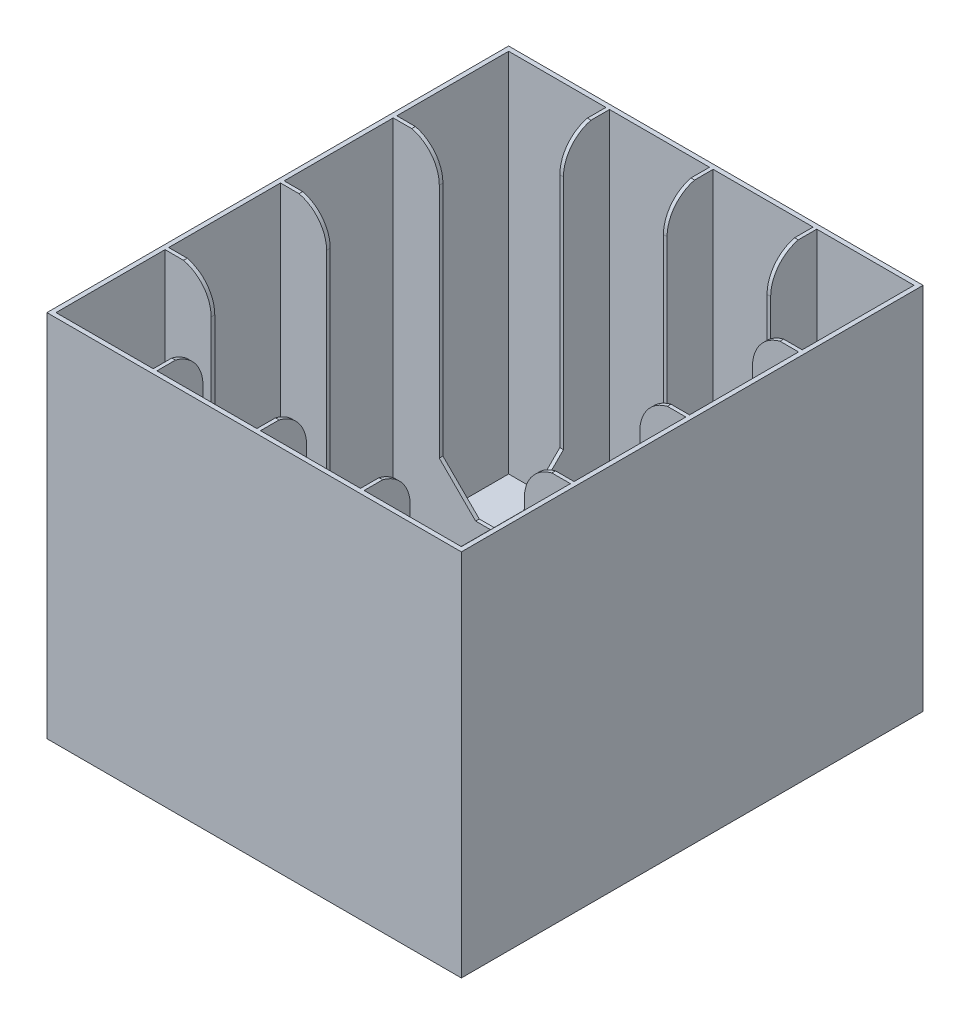
SolidWorks part; units mm, degrees
ref_plane "Front Plane" through (0, 0, 0) normal (0, 0, 1) x (1, 0, 0)
ref_plane "Top Plane" through (0, 0, 0) normal (0, 1, 0) x (1, 0, 0)
ref_plane "Right Plane" through (0, 0, 0) normal (1, 0, 0) x (0, 0, -1)
sketch "Sketch2" plane through (0, 0, 0) normal (0, 1, 0) x (1, 0, 0)
  line L0 (-619.0506, 406.7008) -> (-394.0506, 406.7008)
  line L1 (-620.5506, 408.2008) -> (-392.5506, 408.2008)
  line L2 (-620.5506, 408.2008) -> (-620.5506, 154.2008)
  line L3 (-620.5506, 154.2008) -> (-392.5506, 154.2008)
  line L4 (-392.5506, 408.2008) -> (-392.5506, 154.2008)
  line L5 (-394.0506, 406.7008) -> (-394.0506, 155.7008)
  line L6 (-619.0506, 155.7008) -> (-394.0506, 155.7008)
  line L7 (-619.0506, 406.7008) -> (-619.0506, 155.7008)
  line L8 (-506.5506, 406.7008) -> (-506.5506, 155.7008)
  line L9 (-619.0506, 281.2008) -> (-506.5506, 281.2008)
  line L10 (-506.5506, 281.2008) -> (-394.0506, 281.2008)
  line L11 (-619.0506, 343.2008) -> (-394.0506, 343.2008)
  line L12 (-619.0506, 217.7008) -> (-394.0506, 217.7008)
  line L13 (-563.5506, 406.7008) -> (-563.5506, 155.7008)
  line L14 (-449.5506, 155.7008) -> (-449.5506, 406.7008)
  line L15 (-618.0506, 405.7008) -> (-618.0506, 156.7008)
  line L16 (-618.0506, 156.7008) -> (-395.0506, 156.7008)
  line L17 (-395.0506, 405.7008) -> (-395.0506, 156.7008)
  line L18 (-618.0506, 405.7008) -> (-395.0506, 405.7008)
  line L19 (-562.5506, 406.7008) -> (-562.5506, 155.7008)
  line L20 (-619.0506, 344.2008) -> (-394.0506, 344.2008)
  line L21 (-505.5506, 406.7008) -> (-505.5506, 155.7008)
  line L22 (-619.0506, 282.2008) -> (-506.5506, 282.2008)
  line L23 (-506.5506, 282.2008) -> (-394.0506, 282.2008)
  line L24 (-450.5506, 155.7008) -> (-450.5506, 406.7008)
  line L25 (-619.0506, 218.7008) -> (-394.0506, 218.7008)
  line L26 (-620.0506, 407.7008) -> (-620.0506, 154.7008)
  line L27 (-620.0506, 154.7008) -> (-393.0506, 154.7008)
  line L28 (-393.0506, 407.7008) -> (-393.0506, 154.7008)
  line L29 (-620.0506, 407.7008) -> (-393.0506, 407.7008)
  line L30 (-564.5506, 406.7008) -> (-564.5506, 155.7008)
  line L31 (-619.0506, 342.2008) -> (-394.0506, 342.2008)
  line L32 (-507.5506, 406.7008) -> (-507.5506, 155.7008)
  line L33 (-619.0506, 280.2008) -> (-506.5506, 280.2008)
  line L34 (-506.5506, 280.2008) -> (-394.0506, 280.2008)
  line L35 (-448.5506, 155.7008) -> (-448.5506, 406.7008)
  line L36 (-619.0506, 216.7008) -> (-394.0506, 216.7008)
  dimension "D1" = 228
  dimension "D2" = 254
  dimension "D4" = 114
  dimension "D5" = 114
  dimension "D6" = 127
  dimension "D7" = 63.5
  dimension "D8" = 63.5
  dimension "D9" = 57
  dimension "D10" = 57
  dimension "D3" = 1.5
  dimension "D11" = 1
  dimension "D12" = 1
extrude "Boss-Extrude1" add sketch "Sketch2" against normal blind 1.6 contours L4 L3 L2 L1
extrude "Boss-Extrude2" add sketch "Sketch2<6>" along normal blind 202 contours L4 L1 L2 L3 L26 L29 L28 L27 | L29 L26 L27 L28 L7 L0 L5 L6 | L18 L24 L0 L21 | L32 L0 L19 L18 | L0 L32 L18 L8 | L21 L0 L8 L18 | L30 L0 L7 L20 L15 L18 | L0 L30 L18 L13 | L19 L0 L13 L18 | L20 L7 L11 L15 | L7 L31 L15 L11 | L31 L7 L22 L15 | L22 L7 L9 L15 | L7 L33 L15 L9 | L33 L7 L25 L15 | L25 L7 L12 L15 | L7 L36 L15 L12 | L36 L7 L6 L30 L16 L15 | L32 L16 L19 L6 | L19 L16 L13 L6 | L16 L30 L6 L13 | L16 L32 L6 L8 | L21 L16 L8 L6 | L6 L24 L16 L21 | L24 L6 L14 L16 | L6 L35 L16 L14 | L36 L17 L16 L35 L6 L5 | L17 L36 L5 L12 | L25 L17 L12 L5 | L34 L17 L25 L5 | L20 L17 L11 L5 | L17 L31 L5 L11 | L31 L17 L23 L5 | L35 L18 L17 L20 L5 L0 | L24 L18 L14 L0 | L18 L35 L0 L14 region at (-591.8006, 0, -405.8715) region at (-564.0506, 0, -406.2008) region at (-618.5506, 0, -343.7008) region at (-563.0506, 0, -406.2008) region at (-618.5506, 0, -342.7008) region at (-535.0506, 0, -406.2008) region at (-618.5506, 0, -312.2008) region at (-507.0506, 0, -406.2008) region at (-618.5506, 0, -281.7008) region at (-506.0506, 0, -406.2008) region at (-618.5506, 0, -280.7008) region at (-478.0506, 0, -406.2008) region at (-618.5506, 0, -249.4508) region at (-450.0506, 0, -406.2008) region at (-618.5506, 0, -218.2008) region at (-449.0506, 0, -406.2008) region at (-618.5506, 0, -217.2008) region at (-421.3006, 0, -405.8715) region at (-618.5506, 0, -215.8828) region at (-394.5506, 0, -343.7008) region at (-564.0506, 0, -156.2008) region at (-394.5506, 0, -342.7008) region at (-563.0506, 0, -156.2008) region at (-394.5506, 0, -312.2008) region at (-535.0506, 0, -156.2008) region at (-507.0506, 0, -156.2008) region at (-506.0506, 0, -156.2008) region at (-394.5506, 0, -249.4508) region at (-478.0506, 0, -156.2008) region at (-394.5506, 0, -218.2008) region at (-450.0506, 0, -156.2008) region at (-394.5506, 0, -217.2008) region at (-449.0506, 0, -156.2008) region at (-394.8686, 0, -186.2008) region at (-506.5506, 0, -407.8595) region at (-506.5506, 0, -407.3609)
sketch "Sketch2<6>" plane through (0, 0, 0) normal (0, 1, 0) x (1, 0, 0) same geometry as "Sketch2"
extrude "Boss-Extrude6" add sketch "Sketch2<7>" along normal blind 202 contours L36 L14 L16 L35 | L36 L24 L16 L14 region at (-450.0506, 0, -186.7008) region at (-449.0506, 0, -186.7008)
sketch "Sketch2<7>" plane through (0, 0, 0) normal (0, 1, 0) x (1, 0, 0) same geometry as "Sketch2"
extrude "Boss-Extrude7" add sketch "Sketch2<8>" along normal blind 202 contours L17 L34 L5 L10 | L23 L17 L10 L5 | L35 L10 L17 L23 | L35 L34 L17 L10 region at (-394.5506, 0, -281.7008) region at (-421.8006, 0, -281.7008) region at (-394.5506, 0, -280.7008) region at (-421.8006, 0, -280.7008)
sketch "Sketch2<8>" plane through (0, 0, 0) normal (0, 1, 0) x (1, 0, 0) same geometry as "Sketch2"
extrude "Boss-Extrude8" add sketch "Sketch2<9>" along normal blind 202 contours L35 L11 L17 L20 | L35 L31 L17 L11 | L11 L24 L20 L21 | L21 L31 L24 L11 | L24 L31 L14 L11 | L24 L11 L14 L20 | L11 L35 L20 L14 | L31 L35 L11 L14 region at (-478.0506, 0, -343.7008) region at (-450.0506, 0, -343.7008) region at (-478.0506, 0, -342.7008) region at (-449.0506, 0, -343.7008) region at (-450.0506, 0, -342.7008) region at (-421.8006, 0, -343.7008) region at (-449.0506, 0, -342.7008) region at (-421.8006, 0, -342.7008)
sketch "Sketch2<9>" plane through (0, 0, 0) normal (0, 1, 0) x (1, 0, 0) same geometry as "Sketch2"
extrude "Boss-Extrude12" add sketch "Sketch2<10>" along normal blind 202 contours L20 L35 L18 L14 | L24 L20 L14 L18 region at (-450.0506, 0, -374.9508) region at (-449.0506, 0, -374.9508)
sketch "Sketch2<10>" plane through (0, 0, 0) normal (0, 1, 0) x (1, 0, 0) same geometry as "Sketch2"
extrude "Boss-Extrude13" add sketch "Sketch2<11>" along normal blind 202 contours L23 L35 L31 L14 | L31 L24 L23 L14 | L10 L35 L23 L14 | L24 L10 L14 L23 | L24 L34 L14 L10 | L34 L24 L25 L14 | L25 L35 L34 L14 | L34 L35 L10 L14 region at (-450.0506, 0, -312.2008) region at (-449.0506, 0, -312.2008) region at (-450.0506, 0, -281.7008) region at (-449.0506, 0, -281.7008) region at (-450.0506, 0, -280.7008) region at (-449.0506, 0, -280.7008) region at (-450.0506, 0, -249.4508) region at (-449.0506, 0, -249.4508)
sketch "Sketch2<11>" plane through (0, 0, 0) normal (0, 1, 0) x (1, 0, 0) same geometry as "Sketch2"
extrude "Boss-Extrude14" add sketch "Sketch2<12>" along normal blind 202 contours L35 L12 L17 L25 | L35 L36 L17 L12 | L25 L24 L12 L14 | L24 L36 L14 L12 | L14 L36 L35 L12 | L12 L35 L25 L14 | L25 L21 L12 L24 | L21 L36 L24 L12 region at (-478.0506, 0, -218.2008) region at (-450.0506, 0, -218.2008) region at (-478.0506, 0, -217.2008) region at (-449.0506, 0, -218.2008) region at (-450.0506, 0, -217.2008) region at (-421.8006, 0, -218.2008) region at (-449.0506, 0, -217.2008) region at (-421.8006, 0, -217.2008)
sketch "Sketch2<12>" plane through (0, 0, 0) normal (0, 1, 0) x (1, 0, 0) same geometry as "Sketch2"
extrude "Boss-Extrude19" add sketch "Sketch2<13>" along normal blind 202 contours L10 L24 L23 L21 | L21 L34 L24 L10 | L22 L32 L9 L8 | L32 L33 L8 L9 | L8 L34 L21 L10 | L23 L8 L10 L21 region at (-507.0506, 0, -281.7008) region at (-506.0506, 0, -281.7008) region at (-507.0506, 0, -280.7008) region at (-478.0506, 0, -281.7008) region at (-506.0506, 0, -280.7008) region at (-478.0506, 0, -280.7008)
sketch "Sketch2<13>" plane through (0, 0, 0) normal (0, 1, 0) x (1, 0, 0) same geometry as "Sketch2"
extrude "Boss-Extrude25" add sketch "Sketch2<14>" along normal blind 202 contours L34 L8 L25 L21 | L33 L32 L25 L8 | L25 L8 L12 L21 | L25 L32 L12 L8 | L32 L36 L8 L12 | L8 L36 L21 L12 region at (-507.0506, 0, -249.4508) region at (-506.0506, 0, -249.4508) region at (-507.0506, 0, -218.2008) region at (-506.0506, 0, -218.2008) region at (-507.0506, 0, -217.2008) region at (-506.0506, 0, -217.2008)
sketch "Sketch2<14>" plane through (0, 0, 0) normal (0, 1, 0) x (1, 0, 0) same geometry as "Sketch2"
extrude "Boss-Extrude26" add sketch "Sketch2<17>" along normal blind 202 contours L36 L8 L16 L21 | L36 L32 L16 L8 | L19 L36 L32 L12 | L32 L25 L19 L12 region at (-535.0506, 0, -218.2008) region at (-535.0506, 0, -217.2008) region at (-507.0506, 0, -186.7008) region at (-506.0506, 0, -186.7008)
sketch "Sketch2<17>" plane through (0, 0, 0) normal (0, 1, 0) x (1, 0, 0) same geometry as "Sketch2"
extrude "Boss-Extrude27" add sketch "Sketch2<18>" along normal blind 202 contours L33 L13 L25 L19 | L33 L30 L25 L13 | L25 L30 L12 L13 | L25 L13 L12 L19 | L13 L36 L19 L12 | L30 L36 L13 L12 | L36 L30 L16 L13 | L36 L13 L16 L19 region at (-564.0506, 0, -249.4508) region at (-563.0506, 0, -249.4508) region at (-564.0506, 0, -218.2008) region at (-563.0506, 0, -218.2008) region at (-564.0506, 0, -217.2008) region at (-563.0506, 0, -217.2008) region at (-564.0506, 0, -186.7008) region at (-563.0506, 0, -186.7008)
sketch "Sketch2<18>" plane through (0, 0, 0) normal (0, 1, 0) x (1, 0, 0) same geometry as "Sketch2"
extrude "Boss-Extrude36" add sketch "Sketch2<21>" along normal blind 202 contours L15 L33 L30 L9 | L30 L22 L15 L9 | L30 L33 L13 L9 | L22 L30 L9 L13 region at (-591.3006, 0, -281.7008) region at (-564.0506, 0, -281.7008) region at (-591.3006, 0, -280.7008) region at (-564.0506, 0, -280.7008)
sketch "Sketch2<21>" plane through (0, 0, 0) normal (0, 1, 0) x (1, 0, 0) same geometry as "Sketch2"
extrude "Boss-Extrude40" add sketch "Sketch2<23>" along normal blind 202 contours L19 L33 L32 L9 | L32 L22 L19 L9 | L31 L32 L22 L8 | L31 L8 L23 L21 | L8 L31 L21 L11 | L21 L20 L8 L11 | L20 L32 L11 L8 | L11 L32 L31 L8 | L32 L11 L19 L31 | L32 L20 L19 L11 | L21 L18 L8 L20 | L18 L32 L20 L8 | L21 L0 L8 L18 | L0 L32 L18 L8 | L22 L13 L9 L19 | L13 L33 L19 L9 region at (-507.0506, 0, -406.2008) region at (-506.0506, 0, -406.2008) region at (-507.0506, 0, -374.9508) region at (-535.0506, 0, -343.7008) region at (-506.0506, 0, -374.9508) region at (-507.0506, 0, -343.7008) region at (-535.0506, 0, -342.7008) region at (-506.0506, 0, -343.7008) region at (-507.0506, 0, -342.7008) region at (-563.0506, 0, -281.7008) region at (-506.0506, 0, -342.7008) region at (-507.0506, 0, -312.2008) region at (-535.0506, 0, -281.7008) region at (-563.0506, 0, -280.7008) region at (-506.0506, 0, -312.2008) region at (-535.0506, 0, -280.7008)
sketch "Sketch2<23>" plane through (0, 0, 0) normal (0, 1, 0) x (1, 0, 0) same geometry as "Sketch2"
extrude "Boss-Extrude41" add sketch "Sketch2<24>" along normal blind 202 contours L15 L36 L30 L12 | L30 L25 L15 L12 | L15 L31 L30 L11 | L30 L20 L15 L11 | L20 L30 L11 L13 | L30 L31 L13 L11 | L13 L31 L19 L11 | L20 L13 L11 L19 | L13 L20 L19 L18 | L18 L30 L20 L13 | L31 L30 L22 L13 | L31 L13 L22 L19 region at (-564.0506, 0, -374.9508) region at (-591.3006, 0, -343.7008) region at (-563.0506, 0, -374.9508) region at (-564.0506, 0, -343.7008) region at (-591.3006, 0, -342.7008) region at (-563.0506, 0, -343.7008) region at (-564.0506, 0, -342.7008) region at (-563.0506, 0, -342.7008) region at (-564.0506, 0, -312.2008) region at (-563.0506, 0, -312.2008) region at (-591.3006, 0, -218.2008) region at (-591.3006, 0, -217.2008)
sketch "Sketch2<24>" plane through (0, 0, 0) normal (0, 1, 0) x (1, 0, 0) same geometry as "Sketch2"
sketch "Sketch3" plane through (0, 202, 0) normal (0, 1, 0) x (1, 0, 0)
  line L0 (-392.5506, 408.2008) -> (-392.5506, 154.2008) construction
  line L1 (-592.7033, 380.3534) -> (-420.398, 380.3534)
  line L2 (-592.7033, 380.3534) -> (-592.7033, 182.0481)
  line L3 (-592.7033, 182.0481) -> (-420.398, 182.0481)
  line L4 (-420.398, 380.3534) -> (-420.398, 182.0481)
  line L5 (-620.5506, 408.2008) -> (-620.5506, 154.2008) construction
  line L6 (-620.5506, 408.2008) -> (-392.5506, 408.2008) construction
  line L7 (-620.5506, 154.2008) -> (-392.5506, 154.2008) construction
  dimension "D1" = 27.8473
  dimension "D2" = 27.8473
  dimension "D3" = 27.8473
  dimension "D4" = 27.8473
extrude "Cut-Extrude1" cut sketch "Sketch3" against normal blind 170
chamfer "Chamfer1" distance 20 distance2 20 12 edges at (-563.5506, 32, -182.0481) (-506.5506, 32, -182.0481) (-449.5506, 32, -182.0481) (-420.398, 32, -217.7008) (-420.398, 32, -281.2008) (-420.398, 32, -343.2008) (-592.7033, 32, -217.7008) (-592.7033, 32, -281.2008) (-449.5506, 32, -380.3534) (-506.5506, 32, -380.3534) (-563.5506, 32, -380.3534) (-592.7033, 32, -343.2008)
fillet "Fillet1" radius 20 12 edges at (-420.398, 202, -217.7008) (-420.398, 202, -281.2008) (-420.398, 202, -343.2008) (-449.5506, 202, -380.3534) (-506.5506, 202, -380.3534) (-563.5506, 202, -380.3534) (-592.7033, 202, -343.2008) (-592.7033, 202, -281.2008) (-592.7033, 202, -217.7008) (-563.5506, 202, -182.0481) (-506.5506, 202, -182.0481) (-449.5506, 202, -182.0481)
sketch "Sketch4" plane through (0, 202, 0) normal (0, 1, 0) x (1, 0, 0)
  line L1 (-620.5506, 408.2008) -> (-392.5506, 408.2008)
  line L2 (-620.5506, 408.2008) -> (-620.5506, 154.2008)
  line L3 (-620.5506, 154.2008) -> (-392.5506, 154.2008)
  line L4 (-392.5506, 408.2008) -> (-392.5506, 154.2008)
extrude "Cut-Extrude2" cut sketch "Sketch4" against normal blind 0.6
equation "\"D4@Sketch2\"=\"D1@Sketch2\"/2"
equation "\"D6@Sketch2\"=\"D2@Sketch2\"/2"
equation "\"D7@Sketch2\"=\"D2@Sketch2\"/4"
equation "\"D8@Sketch2\"=\"D2@Sketch2\"/4"
equation "\"D9@Sketch2\"=\"D1@Sketch2\"/4"
equation "\"D10@Sketch2\"=\"D1@Sketch2\"/4"
equation "\"D2@Sketch3\"=\"D1@Sketch3\""
equation "\"D3@Sketch3\"=\"D2@Sketch3\""
equation "\"D4@Sketch3\"=\"D2@Sketch3\""
